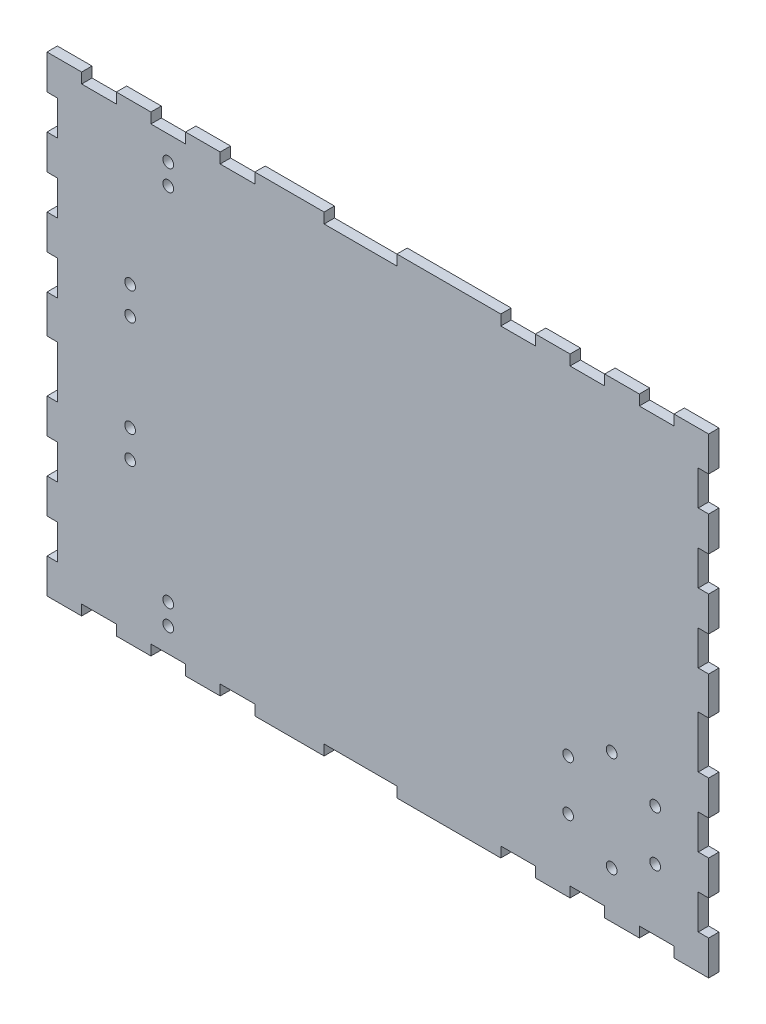
SolidWorks part; units mm, degrees
ref_plane "Front Plane" through (0, 0, 0) normal (0, 0, 1) x (1, 0, 0)
ref_plane "Top Plane" through (0, 0, 0) normal (0, 1, 0) x (1, 0, 0)
ref_plane "Right Plane" through (0, 0, 0) normal (1, 0, 0) x (0, 0, -1)
sketch "Sketch2" plane through (0, 0, 0) normal (0, 0, 1) x (1, 0, 0)
  line L1 (0, 0) -> (191, 0)
  line L2 (0, 0) -> (0, 136)
  line L3 (0, 136) -> (191, 136)
  line L4 (191, 0) -> (191, 136)
  circle A0 centre (35, 16) radius 1.55 construction
  circle A1 centre (35, 10) radius 1.55 construction
  circle A2 centre (24, 46.0692) radius 1.55 construction
  circle A3 centre (24, 54.0692) radius 1.55 construction
  circle A4 centre (24, 81.9308) radius 1.55 construction
  circle A5 centre (24, 89.9308) radius 1.55 construction
  circle A6 centre (35, 120) radius 1.55 construction
  circle A7 centre (35, 126) radius 1.55 construction
  circle A8 centre (175.5574, 35.25) radius 1.55 construction
  circle A9 centre (163, 42.5) radius 1.55 construction
  circle A10 centre (150.4426, 35.25) radius 1.55 construction
  circle A11 centre (150.4426, 20.75) radius 1.55 construction
  circle A12 centre (163, 13.5) radius 1.55 construction
  circle A13 centre (175.5574, 20.75) radius 1.55 construction
  circle A14 centre (35, 16) radius 1.55
  circle A15 centre (35, 10) radius 1.55
  circle A16 centre (24, 46.0692) radius 1.55
  circle A17 centre (24, 54.0692) radius 1.55
  circle A18 centre (24, 81.9308) radius 1.55
  circle A19 centre (24, 89.9308) radius 1.55
  circle A20 centre (35, 120) radius 1.55
  circle A21 centre (35, 126) radius 1.55
  circle A22 centre (175.5574, 35.25) radius 1.55
  circle A23 centre (163, 42.5) radius 1.55
  circle A24 centre (150.4426, 35.25) radius 1.55
  circle A25 centre (150.4426, 20.75) radius 1.55
  circle A26 centre (163, 13.5) radius 1.55
  circle A27 centre (175.5574, 20.75) radius 1.55
extrude "Boss-Extrude1" add sketch "Sketch2" along normal blind 3
ref_axis "Axis1" through (0, 68, 3) along (1, 0, 0)
ref_plane "Plane1" through (0, 68, 0) normal (0, 1, 0) x (1, 0, 0)
ref_axis "Axis2" through (95.5, 0, 3) along (0, 1, 0)
ref_plane "Plane2" through (95.5, 0, 0) normal (1, 0, 0) x (0, 0, -1)
sketch "Sketch3" plane through (0, 0, 3) normal (0, 0, 1) x (1, 0, 0)
  line L0 (0, 3) -> (191, 3) construction
  line L1 (0, 136) -> (0, 0) construction
  line L2 (191, 0) -> (191, 136) construction
  line L3 (0, 0) -> (191, 0) construction
  line L4 (10, 0) -> (10, 3)
  line L5 (20, 0) -> (20, 3)
  line L6 (30, 0) -> (30, 3)
  line L7 (40, 0) -> (40, 3)
  line L8 (50, 0) -> (50, 3)
  line L9 (60, 0) -> (60, 3)
  line L10 (10, 0) -> (20, 0)
  line L11 (20, 3) -> (10, 3)
  line L12 (30, 0) -> (40, 0)
  line L13 (40, 3) -> (30, 3)
  line L14 (50, 0) -> (60, 0)
  line L15 (80, 3) -> (80, 0)
  line L16 (60, 3) -> (50, 3)
  line L17 (181, 0) -> (181, 3)
  line L18 (171, 0) -> (171, 3)
  line L19 (161, 0) -> (161, 3)
  line L20 (151, 0) -> (151, 3)
  line L21 (141, 0) -> (141, 3)
  line L22 (131, 0) -> (131, 3)
  line L23 (181, 0) -> (171, 0)
  line L24 (171, 0) -> (170.9794, -0.0476)
  line L25 (171, 3) -> (181, 3)
  line L26 (181, 3) -> (181.0353, 3.2173)
  line L27 (161, 0) -> (151, 0)
  line L28 (161, 3) -> (151, 3)
  line L29 (141, 0) -> (131, 0)
  line L30 (131, 3) -> (141, 3)
  line L31 (141, 3) -> (140.9859, 2.9583)
  line L32 (101, 0) -> (101, 3)
  line L33 (80, 0) -> (101, 0)
  line L34 (101, 3) -> (80, 3)
  line M15 (0, 0) -> (191, 0)
  dimension "D6" = 20
  dimension "D1" = 3
  dimension "D2" = 10
  dimension "D4" = 10
  dimension "D7" = 30
  dimension "D3" = 6
  dimension "D5" = 6
extrude "Cut-Extrude1" cut sketch "Sketch3" against normal up to next contours L5 L11 L4 M15 | L7 L13 L6 M15 | L9 L16 L8 M15 | L32 L34 L15 M15 | L30 L22 L21 M15 | L19 L28 L20 M15 | L25 L18 L17 M15 region at (176, 1.5, 3) region at (156, 1.5, 3) region at (136, 1.5, 3) region at (90.5, 1.5, 3) region at (55, 1.5, 3) region at (35, 1.5, 3) region at (15, 1.5, 3)
mirror "Mirror1" about plane through (0, 68, 0) normal (0, 1, 0) of "Cut-Extrude1"
sketch "Sketch4" plane through (0, 0, 3) normal (0, 0, 1) x (1, 0, 0)
  line L0 (3, 136) -> (3, 0) construction
  line L1 (10, 136) -> (0, 136) construction
  line L2 (0, 0) -> (10, 0) construction
  line L3 (0, 136) -> (0, 0) construction
  line L4 (0, 126) -> (3, 126)
  line L5 (0, 116) -> (3, 116)
  line L6 (0, 106) -> (3, 106)
  line L7 (0, 96) -> (3, 96)
  line L8 (0, 86) -> (3, 86)
  line L9 (0, 10) -> (3, 10)
  line L10 (0, 20) -> (3, 20)
  line L11 (0, 30) -> (3, 30)
  line L12 (0, 40) -> (3, 40)
  line L13 (0, 50) -> (3, 50)
  line L14 (0, 126) -> (0, 116)
  line L15 (3, 116) -> (3, 126)
  line L16 (0, 106) -> (0, 96)
  line L17 (3, 96) -> (3, 106)
  line L18 (0, 20) -> (0, 10)
  line L19 (3, 10) -> (3, 20)
  line L20 (0, 30) -> (0, 40)
  line L21 (3, 30) -> (3, 40)
  line L22 (0, 65) -> (3, 65)
  line L23 (0, 76) -> (3, 76)
  line L24 (0, 86) -> (0, 76)
  line L25 (3, 76) -> (3, 86)
  line L26 (0, 65) -> (0, 50)
  line L27 (3, 50) -> (3, 65)
  dimension "D1" = 3
  dimension "D2" = 10
  dimension "D4" = 10
  dimension "D6" = 15
  dimension "D3" = 6
  dimension "D5" = 5
extrude "Cut-Extrude2" cut sketch "Sketch4" against normal up to next
mirror "Mirror2" about plane through (95.5, 0, 0) normal (1, 0, 0) of "Cut-Extrude2"
sketch "Sketch6" plane through (0, 0, 3) normal (0, 0, 1) x (1, 0, 0)
  line L0 (116, 0) -> (116, 136) construction
  line L1 (101, 0) -> (131, 0) construction
  line L2 (131, 136) -> (101, 136) construction
  line L3 (191, 68) -> (85, 68) construction
  line L4 (191, 65) -> (191, 76) construction
  dimension "D1" = 106
ref_point "MountPoint-Dif"
